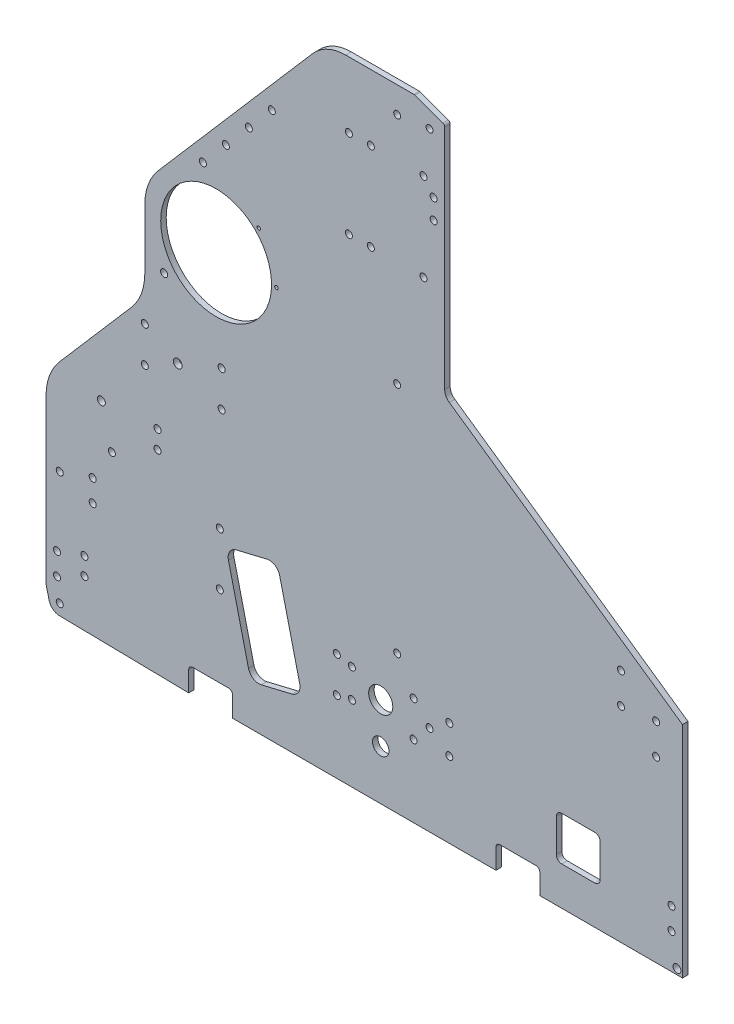
SolidWorks part; units mm, degrees
ref_plane "Front Plane" through (0, 0, 0) normal (0, 0, 1) x (1, 0, 0)
ref_plane "Top Plane" through (0, 0, 0) normal (0, 1, 0) x (1, 0, 0)
ref_plane "Right Plane" through (0, 0, 0) normal (1, 0, 0) x (0, 0, -1)
sketch "Sketch1" plane through (0, 0, 0) normal (0, 0, 1) x (1, 0, 0)
  line L0 (82.55, -20.32) -> (82.55, -6.35)
  line L2 (0, 0) -> (0, 157.48)
  line L4 (368.3, -20.32) -> (368.3, 106.68)
  line L5 (82.55, -6.35) -> (107.95, -6.35)
  line L6 (107.95, -6.35) -> (107.95, -20.32)
  line L7 (107.95, -20.32) -> (260.35, -20.32)
  line L8 (260.35, -20.32) -> (260.35, -6.35)
  line L9 (260.35, -6.35) -> (285.75, -6.35)
  line L10 (285.75, -6.35) -> (285.75, -20.32)
  line L11 (285.75, -20.32) -> (368.3, -20.32)
  line L12 (361.95, 12.7) -> (368.3, 12.7) construction
  line L13 (0, 0) -> (6.35, 0) construction
  line L14 (0.1896, -7.8901) -> (1.7771, -14.2401)
  line L15 (7.8295, -19.0491) -> (82.55, -20.32)
  line L16 (0, 0) -> (0, -6.35)
  line L17 (76.2, 141.605) -> (79.375, 141.605) construction
  line L18 (57.15, 131.2863) -> (101.6, 131.2862) construction
  line L19 (57.15, 131.2863) -> (57.15, 151.9238) construction
  line L20 (101.6, 131.2862) -> (101.6, 151.9237) construction
  line L21 (57.15, 151.9238) -> (101.6, 151.9237) construction
  line L22 (57.15, 131.2863) -> (101.6, 151.9237) construction
  line L23 (101.6, 131.2862) -> (57.15, 151.9238) construction
  line L25 (203.2, 59.805) -> (203.2, 194.805) construction
  line L26 (203.2, 194.805) -> (203.2, 329.805) construction
  line L27 (355.6, 332.105) -> (330.2, 332.105) construction
  line L28 (330.2, 332.105) -> (330.2, 217.805) construction
  line L29 (330.2, 217.805) -> (355.6, 217.805) construction
  line L30 (355.6, 217.805) -> (355.6, 332.105) construction
  line L31 (203.2, 344.805) -> (203.2, 194.805) construction
  line L32 (50.8, 332.105) -> (76.2, 332.105) construction
  line L33 (76.2, 332.105) -> (76.2, 217.805) construction
  line L34 (50.8, 217.805) -> (50.8, 332.105) construction
  line L35 (76.2, 217.805) -> (50.8, 217.805) construction
  line L36 (213.2, 344.805) -> (230.6638, 338.455)
  line L37 (203.2, 344.805) -> (161.925, 344.805)
  line L38 (203.2, 344.805) -> (213.2, 344.805)
  line L39 (348.5362, 344.805) -> (413.4623, 344.805)
  line L40 (348.5362, 344.805) -> (230.6638, 344.805) construction
  line L42 (161.925, 344.805) -> (0, 157.48)
  line L44 (230.6638, 338.455) -> (230.6638, 202.565)
  line L45 (230.6638, 202.565) -> (368.3, 106.68)
  line L46 (213.2, 344.805) -> (-141.0713, 344.805) construction
  circle A0 centre (6.35, 0) radius 2.032
  circle A1 centre (6.35, 12.7) radius 2.032
  circle A2 centre (361.95, 0) radius 2.032
  circle A3 centre (361.95, 12.7) radius 2.032
  arc A5 (1.7771, -14.2401) -> (7.8295, -19.0491) centre (7.9375, -12.7) ccw
  circle A6 centre (7.9375, -12.7) radius 2.032
  arc A7 (0, -6.35) -> (0.1896, -7.8901) centre (6.35, -6.35) ccw
  circle A8 centre (38.1, 78.105) radius 2.032
  circle A9 centre (76.2, 141.605) radius 2.54
  circle A10 centre (101.6, 131.2862) radius 2.032
  circle A11 centre (101.6, 151.9237) radius 2.032
  circle A12 centre (57.15, 151.9238) radius 2.032
  circle A13 centre (57.15, 131.2863) radius 2.032
  circle A15 centre (203.2, 59.805) radius 2
  circle A16 centre (203.2, 194.805) radius 2
  circle A17 centre (203.2, 329.805) radius 2
  circle A18 centre (63.5, 313.055) radius 2.032
  circle A20 centre (355.6, 332.105) radius 2.032
  circle A21 centre (330.2, 332.105) radius 2.032
  circle A22 centre (355.6, 217.805) radius 2.032
  circle A23 centre (330.2, 217.805) radius 2.032
  circle A24 centre (50.8, 332.105) radius 2.032
  circle A25 centre (76.2, 332.105) radius 2.032
  circle A26 centre (50.8, 217.805) radius 2.032
  circle A27 centre (76.2, 217.805) radius 2.032
  circle A28 centre (221.9319, 332.105) radius 2
  circle A29 centre (224.3138, 298.831) radius 2.032
  circle A30 centre (353.06, 100.7351) radius 2.032
  circle A31 centre (332.74, 115.9751) radius 2.032
  circle A32 centre (332.74, 98.1951) radius 2.032
  circle A33 centre (353.06, 82.9551) radius 2.032
  circle A34 centre (117.3562, 280.4276) radius 2.032
  circle A35 centre (104.0678, 265.0548) radius 2.032
  circle A36 centre (90.7795, 249.682) radius 2.032
  circle A38 centre (130.6445, 295.8004) radius 2.032
  circle A39 centre (68.326, 182.9237) radius 2.032
  circle A40 centre (224.3138, 287.401) radius 2.032
  point P82 (203.2, 344.805)
  point P83 (221.9319, 341.63)
  point P90 (368.3, 62.484)
  dimension "D6" = 4.064
  dimension "D10" = 6.35
  dimension "D11" = 4.064
  dimension "D17" = 38.1
  dimension "D27" = 4
  dimension "D31" = 4.064
  dimension "D32" = 41.275
  dimension "D36" = 4.064
  dimension "D47" = 39.624
  dimension "D48" = 4.064
  dimension "D25" = 5.08
  dimension "D26" = 4.064
  dimension "D52" = 4.064
  dimension "D65" = 4.064
  dimension "D2" = 127
  dimension "D3" = 13.97
  dimension "D4" = 25.4
  dimension "D5" = 152.4
  dimension "D7" = 12.7
  dimension "D8" = 6.35
  dimension "D9" = 20.32
  dimension "D12" = 12.7
  dimension "D13" = 1.5875
  dimension "D14" = 82.55
  dimension "D15" = 368.3
  dimension "D16" = 6.35
  dimension "D18" = 98.425
  dimension "D19" = 38.1
  dimension "D20" = 63.5
  dimension "D21" = 3.175
  dimension "D22" = 270
  dimension "D23" = 20.6375
  dimension "D24" = 44.45
  dimension "D28" = 135
  dimension "D29" = 12.7
  dimension "D30" = 15
  dimension "D33" = 63.5
  dimension "D34" = 27.4638
  dimension "D35" = 12.7
  dimension "D37" = 114.3
  dimension "D38" = 25.4
  dimension "D39" = 12.7
  dimension "D40" = 157.48
  dimension "D41" = 142.24
  dimension "D42" = 365.125
  dimension "D43" = 10
  dimension "D44" = 6.35
  dimension "D45" = 31.75
  dimension "D46" = 6.35
  dimension "D49" = 6.35
  dimension "D50" = 203.2
  dimension "D51" = 15.24
  dimension "D53" = 17.78
  dimension "D54" = 17.78
  dimension "D55" = 20.32
  dimension "D56" = 15.24
  dimension "D57" = 92.202
  dimension "D58" = 8.382
  dimension "D59" = 20.32
  dimension "D60" = 20.32
  dimension "D61" = 8.382
  dimension "D62" = 20.32
  dimension "D63" = 8.382
  dimension "D64" = 8.382
  dimension "D66" = 35.052
  dimension "D67" = 68.326
  dimension "D68" = 11.43
extrude "Boss-Extrude1" add sketch "Sketch1" along normal blind 3.175 contours L16 A7 L14 A5 L15 L2 A0 A1 A6 region at (171.3489, 119.5243, 0)
fillet "Fillet1" radius 2.286 4 edges at (285.75, -6.35, 1.5875) (107.95, -6.35, 1.5875) (260.35, -6.35, 1.5875) (82.55, -6.35, 1.5875)
fillet "Fillet2" radius 6.35 1 edges at (230.6638, 202.565, 1.5875)
sketch "Sketch2" plane through (0, 0, 0) normal (0, 0, -1) x (-1, 0, 0)
  circle A0 centre (-100.5528, 71.086) radius 2.032 construction
  circle A1 centre (-100.5528, 40.606) radius 2.032 construction
  circle A2 centre (-22.225, 18.2025) radius 2.032 construction
  circle A3 centre (-22.225, 8.0425) radius 2.032 construction
  circle A4 centre (-100.5528, 71.086) radius 2.032
  circle A5 centre (-100.5528, 40.606) radius 2.032
  circle A6 centre (-22.225, 18.2025) radius 2.032
  circle A7 centre (-22.225, 8.0425) radius 2.032
extrude "Cut-Extrude1" cut sketch "Sketch2" against normal through all
fillet "Fillet3" radius 1.5875 2 edges at (230.6638, 338.455, 1.5875) (213.2, 344.805, 1.5875)
sketch "Sketch3" plane through (0, 0, 3.175) normal (0, 0, 1) x (1, 0, 0)
  line L0 (132.9524, 63.2646) -> (132.7215, 64.2281) construction
  line L1 (128.3814, 66.8897) -> (110.6828, 62.6472) construction
  line L2 (114.5132, 58.4237) -> (126.8822, 61.3887) construction
  line L3 (108.0212, 58.3071) -> (108.2522, 57.3436) construction
  line L4 (131.2006, 57.703) -> (140.0164, 20.9265) construction
  line L5 (144.0993, 16.7636) -> (132.9524, 63.2646) construction
  line L6 (108.2522, 57.3436) -> (119.3991, 10.8426) construction
  line L7 (121.1509, 16.4042) -> (112.3351, 53.1807) construction
  line L8 (119.3991, 10.8426) -> (119.6301, 9.8791) construction
  line L9 (144.3303, 15.8001) -> (144.0993, 16.7636) construction
  line L10 (137.8383, 15.6835) -> (125.4694, 12.7185) construction
  line L11 (123.9701, 7.2175) -> (141.6687, 11.4601) construction
  line L12 (132.9524, 63.2646) -> (132.7215, 64.2281)
  line L13 (128.3814, 66.8897) -> (110.6828, 62.6472)
  line L14 (114.5132, 58.4237) -> (126.8822, 61.3887)
  line L15 (108.0212, 58.3071) -> (108.2522, 57.3436)
  line L16 (131.2006, 57.703) -> (140.0164, 20.9265)
  line L17 (144.0993, 16.7636) -> (132.9524, 63.2646)
  line L18 (108.2522, 57.3436) -> (119.3991, 10.8426)
  line L19 (121.1509, 16.4042) -> (112.3351, 53.1807)
  line L20 (119.3991, 10.8426) -> (119.6301, 9.8791)
  line L21 (144.3303, 15.8001) -> (144.0993, 16.7636)
  line L22 (137.8383, 15.6835) -> (125.4694, 12.7185)
  line L23 (123.9701, 7.2175) -> (141.6687, 11.4601)
  line L24 (127.7894, 69.3598) -> (110.0908, 65.1172)
  line L25 (105.5512, 57.715) -> (105.7822, 56.7515)
  line L26 (105.7822, 56.7515) -> (116.9291, 10.2505)
  line L27 (116.9291, 10.2505) -> (117.16, 9.287)
  line L28 (124.5622, 4.7475) -> (142.2608, 8.99)
  line L29 (146.8003, 16.3922) -> (146.5694, 17.3557)
  line L30 (146.5694, 17.3557) -> (135.4225, 63.8567)
  line L31 (135.4225, 63.8567) -> (135.1915, 64.8202)
  line L32 (14.605, -0.1369) -> (103.7278, 32.3011) construction
  line L33 (14.605, -0.1369) -> (103.7278, 32.3011)
  line L35 (-39.6666, 74.7152) -> (103.7278, 126.9065) construction
  arc A0 (132.7215, 64.2281) -> (128.6308, 66.9403) centre (129.2206, 63.3889) ccw construction
  arc A1 (110.6828, 62.6472) -> (110.4377, 62.5791) centre (111.522, 59.1463) ccw construction
  arc A2 (128.6308, 66.9403) -> (128.3814, 66.8897) centre (129.2206, 63.3889) ccw construction
  arc A3 (110.4377, 62.5791) -> (108.0212, 58.3071) centre (111.522, 59.1463) ccw construction
  arc A4 (119.6301, 9.8791) -> (123.7207, 7.1669) centre (123.1309, 10.7183) ccw construction
  arc A5 (141.9139, 11.5281) -> (144.3303, 15.8001) centre (140.8295, 14.9609) ccw construction
  arc A6 (141.6687, 11.4601) -> (141.9139, 11.5281) centre (140.8295, 14.9609) ccw construction
  arc A7 (123.7207, 7.1669) -> (123.9701, 7.2175) centre (123.1309, 10.7183) ccw construction
  arc A8 (132.7215, 64.2281) -> (128.6308, 66.9403) centre (129.2206, 63.3889) ccw
  arc A9 (110.6828, 62.6472) -> (110.4377, 62.5791) centre (111.522, 59.1463) ccw
  arc A10 (128.6308, 66.9403) -> (128.3814, 66.8897) centre (129.2206, 63.3889) ccw
  arc A11 (110.4377, 62.5791) -> (108.0212, 58.3071) centre (111.522, 59.1463) ccw
  arc A12 (119.6301, 9.8791) -> (123.7207, 7.1669) centre (123.1309, 10.7183) ccw
  arc A13 (141.9139, 11.5281) -> (144.3303, 15.8001) centre (140.8295, 14.9609) ccw
  arc A14 (141.6687, 11.4601) -> (141.9139, 11.5281) centre (140.8295, 14.9609) ccw
  arc A15 (123.7207, 7.1669) -> (123.9701, 7.2175) centre (123.1309, 10.7183) ccw
  arc A16 (110.0908, 65.1172) -> (109.6726, 65.0012) centre (111.522, 59.1463) ccw
  arc A17 (109.6726, 65.0012) -> (105.5512, 57.715) centre (111.522, 59.1463) ccw
  arc A18 (117.16, 9.287) -> (124.1369, 4.6613) centre (123.1309, 10.7183) ccw
  arc A19 (124.1369, 4.6613) -> (124.5622, 4.7475) centre (123.1309, 10.7183) ccw
  arc A20 (142.2608, 8.99) -> (142.6789, 9.1061) centre (140.8295, 14.9609) ccw
  arc A21 (142.6789, 9.1061) -> (146.8003, 16.3922) centre (140.8295, 14.9609) ccw
  arc A22 (135.1915, 64.8202) -> (128.2147, 69.446) centre (129.2206, 63.3889) ccw
  arc A23 (128.2147, 69.446) -> (127.7894, 69.3598) centre (129.2206, 63.3889) ccw
  circle A24 centre (64.5259, 102.9405) radius 2.032 construction
  circle A25 centre (64.5259, 92.5258) radius 2.032 construction
  circle A26 centre (133.35, 208.2281) radius 1.016 construction
  circle A33 centre (26.9875, 46.9531) radius 2.032
  circle A34 centre (26.9875, 59.6531) radius 2.032
  circle A35 centre (7.9375, 53.3031) radius 2.032
  circle A36 centre (7.9375, 53.3031) radius 2.032 construction
  circle A37 centre (32.0306, 100.8109) radius 31.75 construction
  circle A38 centre (32.0306, 100.8109) radius 2.286
  circle A39 centre (123.1207, 232.9238) radius 1.016 construction
  circle A40 centre (64.5259, 102.9405) radius 2.032
  circle A41 centre (64.5259, 92.5258) radius 2.032
  circle A42 centre (133.35, 208.2281) radius 1.016
  circle A43 centre (123.1207, 232.9238) radius 1.016
  circle A44 centre (26.9875, 59.6531) radius 2.032 construction
  circle A45 centre (26.9875, 46.9531) radius 2.032 construction
  ellipse E0 centre (124.5974, 48.8487) end of major axis (128.5376, 61.3578) minor radius 6 (131.2006, 57.703) -> (126.8822, 61.3887) ccw construction
  ellipse E1 centre (122.2349, 48.2824) end of major axis (113.0518, 57.6456) minor radius 6 (114.5132, 58.4237) -> (112.3351, 53.1807) ccw construction
  ellipse E2 centre (127.7541, 25.2585) end of major axis (131.6942, 37.7675) minor radius 6 (121.1509, 16.4042) -> (125.4694, 12.7185) ccw construction
  ellipse E3 centre (130.1166, 25.8248) end of major axis (139.2998, 16.4616) minor radius 6 (137.8383, 15.6835) -> (140.0164, 20.9265) ccw construction
  ellipse E4 centre (124.5974, 48.8487) end of major axis (128.5376, 61.3578) minor radius 6 (131.2006, 57.703) -> (126.8822, 61.3887) ccw
  ellipse E5 centre (122.2349, 48.2824) end of major axis (131.4181, 38.9192) minor radius 6 (114.5132, 58.4237) -> (112.3351, 53.1807) ccw
  ellipse E6 centre (127.7541, 25.2585) end of major axis (123.8139, 12.7495) minor radius 6 (121.1509, 16.4042) -> (125.4694, 12.7185) ccw
  ellipse E7 centre (130.1166, 25.8248) end of major axis (139.2998, 16.4616) minor radius 6 (137.8383, 15.6835) -> (140.0164, 20.9265) ccw
  point P115 (32.0306, 100.8109)
  dimension "D3" = 63.5
  dimension "D4" = 4.572
  dimension "D2" = 88.9
  dimension "D1" = 2.54
extrude "Cut-Extrude2" cut sketch "Sketch3" against normal through all contours A22 A23 L24 A16 A17 L25 L26 L27 A18 A19 L28 A20 A21 L29 L30 L31 A15 A12 L20 L18 L15 A11 A9 L13 A10 A8 L12 L17 L21 A13 A14 L23 | A12 A15 L23 A14 A13 L21 L17 L12 A8 A10 L13 A9 A11 L15 L18 L20 E7 L22 E6 L19 E5 L14 E4 L16 | L22 E7 L16 E4 L14 E5 L19 E6 | A38 | A41 | A40 | A35 | A34 | A33 | A43 | A42 region at (137.844, 39.8506, 3.175) region at (126.1758, 37.0536, 3.175) region at (128.1544, 68.6507, 3.175) region at (32.0306, 100.8109, 3.175) region at (64.5259, 102.9405, 3.175) region at (64.5259, 92.5258, 3.175)
sketch "Sketch4" plane through (0, 0, 3.175) normal (0, 0, 1) x (1, 0, 0)
  line L0 (57.15, 151.9238) -> (101.6, 151.9237) construction
  line L1 (168.275, 21.4312) -> (212.725, 21.4312) construction
  line L2 (168.275, 21.4312) -> (168.275, 42.0687) construction
  line L3 (168.275, 42.0687) -> (212.725, 42.0687) construction
  line L4 (212.725, 21.4312) -> (212.725, 42.0687) construction
  line L5 (168.275, 21.4312) -> (212.725, 42.0687) construction
  line L6 (168.275, 42.0687) -> (212.725, 21.4312) construction
  line L7 (57.15, 131.2863) -> (57.15, 151.9238) construction
  line L8 (107.95, -20.32) -> (260.35, -20.32) construction
  line L9 (193.675, 31.75) -> (177.005, 31.75) construction
  line L10 (190.5, 31.75) -> (193.675, 31.75) construction
  line L11 (6.35, 12.7) -> (361.95, 12.7) construction
  line L12 (107.95, -6.35) -> (107.95, -20.32) construction
  line L13 (193.675, 31.75) -> (220.6625, 31.75) construction
  line L14 (177.005, 23.4569) -> (177.005, 40.0431) construction
  line L15 (213.2, 44.805) -> (193.2, 44.805) construction
  line L16 (213.2, 44.805) -> (213.2, 344.805) construction
  line L17 (213.2, 344.805) -> (193.2, 344.805) construction
  line L18 (193.2, 44.805) -> (193.2, 344.805) construction
  line L19 (213.2, 44.805) -> (193.2, 344.805) construction
  line L20 (213.2, 344.805) -> (193.2, 44.805) construction
  line L21 (226.9319, 332.105) -> (226.9319, 31.75) construction
  line L22 (237.33, 40.0431) -> (233.3612, 40.0431) construction
  line L23 (237.33, 23.4569) -> (233.3612, 23.4569) construction
  circle A0 centre (168.275, 42.0687) radius 2.032
  circle A1 centre (212.725, 42.0687) radius 2.032
  circle A2 centre (212.725, 21.4312) radius 2.032
  circle A3 centre (168.275, 21.4312) radius 2.032
  circle A4 centre (193.675, 31.75) radius 6.985
  circle A7 centre (220.6625, 31.75) radius 14.2875 construction
  circle A8 centre (193.675, 31.75) radius 12.7 construction
  circle A9 centre (177.005, 40.0431) radius 2.032
  circle A10 centre (177.005, 23.4569) radius 2.032
  circle A11 centre (237.33, 40.0431) radius 2.032 construction
  circle A12 centre (237.33, 23.4569) radius 2.032 construction
  circle A13 centre (193.675, 8.4667) radius 4.7625
  circle A14 centre (221.9319, 31.75) radius 2.032
  circle A15 centre (221.9319, 31.75) radius 5 construction
  circle A16 centre (221.9319, 332.105) radius 5 construction
  circle A17 centre (233.3612, 23.4569) radius 2.032
  circle A18 centre (233.3612, 40.0431) radius 2.032
  point P0 (190.5, 31.75)
  point P26 (203.2, 194.805)
  point P38 (177.005, 31.75)
  dimension "D1" = 4.064
  dimension "D4" = 13.97
  dimension "D7" = 9.525
  dimension "D10" = 25.4
  dimension "D11" = 28.575
  dimension "D16" = 10
  dimension "D17" = 4.064
  dimension "D18" = 10
  dimension "D2" = 52.07
  dimension "D3" = 3.175
  dimension "D5" = 82.55
  dimension "D6" = 26.9875
  dimension "D8" = 20
  dimension "D9" = 300
  dimension "D12" = 16.67
  dimension "D13" = 16.5862
  dimension "D14" = 60.325
  dimension "D15" = 23.2833
  dimension "D19" = 3.9688
extrude "Cut-Extrude3" cut sketch "Sketch4" against normal through all
sketch "Sketch5" plane through (0, 0, -187.325) normal (0, 0, -1) x (-1, 0, 0)
  line L0 (-57.15, 223.5947) -> (-57.15, 165.3337)
  line L1 (-161.925, 344.805) -> (-52.7201, 218.4699) construction
  line L2 (-57.15, 165.3337) -> (0, 99.219)
  line L3 (0, -6.35) -> (0, 157.48) construction
  line L4 (-50.4199, 215.8089) -> (0, 157.48) construction
  line L5 (-50.4199, 215.8089) -> (0, 157.48) construction
  line L6 (-57.15, 223.5947) -> (0, 157.48)
  line L7 (0, 157.48) -> (0, 99.219)
  circle A0 centre (-98.425, 208.2281) radius 32.0675
  circle A1 centre (-365.125, -17.145) radius 2.286 construction
  circle A2 centre (-365.125, -17.145) radius 2.286
  dimension "D3" = 64.135
  dimension "D1" = 38.1
  dimension "D2" = 57.15
  dimension "D4" = 41.275
  dimension "D5" = 41.275
extrude "Cut-Extrude5" cut sketch "Sketch5" against normal through all contours A0 | L7 L6 L0 L2 | A2 region at (28.575, 161.4068, -187.325) region at (98.425, 208.2281, -187.325)
fillet "Fillet4" radius 31.75 3 edges at (0, 99.219, 1.5875) (57.15, 165.3337, 1.5875) (57.15, 223.5947, 1.5875)
sketch "Sketch6" plane through (0, 0, 3.175) normal (0, 0, 1) x (1, 0, 0)
  line L0 (285.75, -20.32) -> (368.3, -20.32) construction
  line L1 (298.45, 27.305) -> (317.5, 27.305)
  line L2 (295.275, 24.13) -> (295.275, 5.08)
  line L3 (298.45, 1.905) -> (317.5, 1.905)
  line L4 (320.675, 24.13) -> (320.675, 5.08)
  line L5 (295.275, 27.305) -> (320.675, 1.905) construction
  line L6 (295.275, 1.905) -> (320.675, 27.305) construction
  line L7 (368.3, -20.32) -> (368.3, 106.68) construction
  arc A0 (295.275, 5.08) -> (298.45, 1.905) centre (298.45, 5.08) ccw
  arc A1 (317.5, 1.905) -> (320.675, 5.08) centre (317.5, 5.08) ccw
  arc A2 (317.5, 27.305) -> (320.675, 24.13) centre (317.5, 24.13) cw
  arc A3 (298.45, 27.305) -> (295.275, 24.13) centre (298.45, 24.13) ccw
  point P0 (307.975, 14.605)
  dimension "D2" = 3.175
  dimension "D1" = 25.4
  dimension "D3" = 22.225
  dimension "D4" = 47.625
extrude "Cut-Extrude6" cut sketch "Sketch6" against normal through all
fillet "Fillet5" radius 25.4 1 edges at (161.925, 344.805, 1.5875)
sketch "Sketch8" plane through (0, 0, 0) normal (0, 0, -1) x (-1, 0, 0)
  circle A0 centre (-187.96, 306.705) radius 2.032 construction
  arc A1 (-176.3652, 304.9998) -> (-176.3652, 308.4102) centre (-175.26, 306.705) ccw construction
  arc A2 (-219.0586, 304.7695) -> (-219.0586, 308.6405) centre (-218.44, 306.705) ccw construction
  circle A3 centre (-205.74, 306.705) radius 2.032 construction
  arc A4 (-219.0586, 253.9695) -> (-219.0586, 257.8405) centre (-218.44, 255.905) ccw construction
  circle A5 centre (-205.74, 255.905) radius 2.032 construction
  circle A6 centre (-187.96, 255.905) radius 2.032 construction
  arc A7 (-176.3652, 254.1998) -> (-176.3652, 257.6102) centre (-175.26, 255.905) ccw construction
  circle A8 centre (-187.96, 306.705) radius 2.032
  arc A9 (-176.3652, 304.9998) -> (-176.3652, 308.4102) centre (-175.26, 306.705) ccw
  arc A10 (-219.0586, 304.7695) -> (-219.0586, 308.6405) centre (-218.44, 306.705) ccw
  circle A11 centre (-205.74, 306.705) radius 2.032
  arc A12 (-219.0586, 253.9695) -> (-219.0586, 257.8405) centre (-218.44, 255.905) ccw
  circle A13 centre (-205.74, 255.905) radius 2.032
  circle A14 centre (-187.96, 255.905) radius 2.032
  arc A15 (-176.3652, 254.1998) -> (-176.3652, 257.6102) centre (-175.26, 255.905) ccw
  circle A16 centre (-218.44, 306.705) radius 2.032
  circle A17 centre (-175.26, 306.705) radius 2.032
  circle A18 centre (-175.26, 255.905) radius 2.032
  circle A19 centre (-218.44, 255.905) radius 2.032
  circle A20 centre (-218.44, 306.705) radius 3.9688
  circle A21 centre (-205.74, 306.705) radius 3.9687
  circle A22 centre (-175.26, 306.705) radius 3.9687
  circle A23 centre (-218.44, 255.905) radius 3.9687
  circle A24 centre (-205.74, 255.905) radius 3.9687
  circle A25 centre (-187.96, 255.905) radius 3.9688
  circle A26 centre (-175.26, 255.905) radius 3.9687
  circle A27 centre (-187.96, 306.705) radius 3.9687
  dimension "D1" = 7.9375
extrude "Cut-Extrude7" cut sketch "Sketch8" against normal through all contours A10 A16 | A9 A17 | A15 A18 | A12 A19 | A8 | A14 region at (175.26, 306.705, 0) region at (218.44, 306.705, 0) region at (218.44, 255.905, 0) region at (175.26, 255.905, 0)
